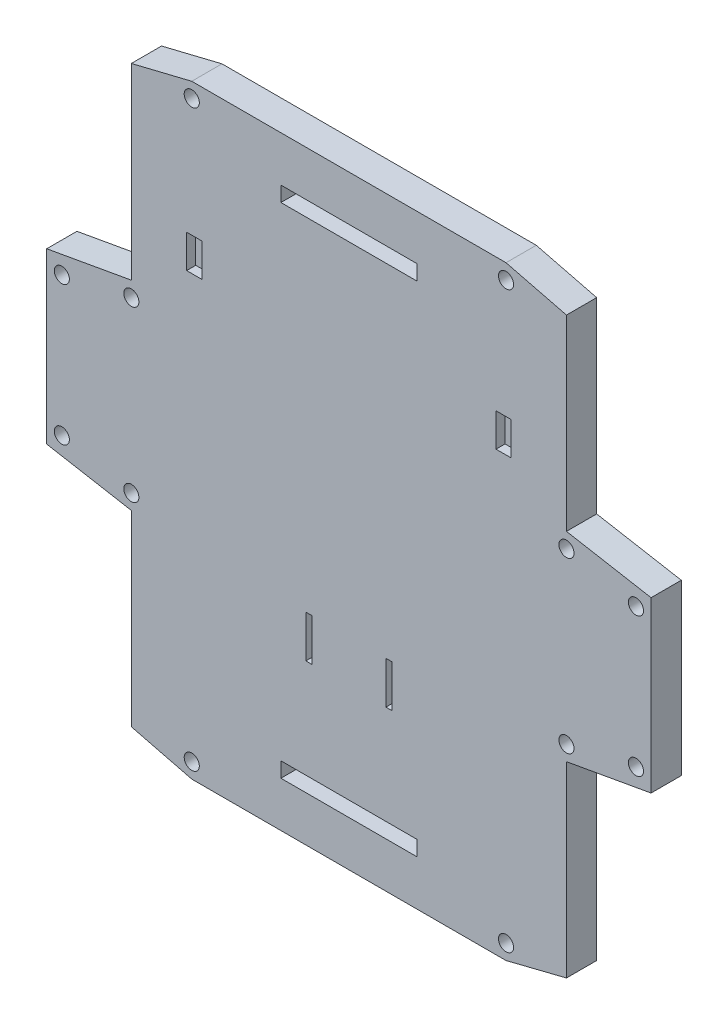
SolidWorks part; units mm, degrees
ref_plane "Front Plane" through (0, 0, 0) normal (0, 0, 1) x (1, 0, 0)
ref_plane "Top Plane" through (0, 0, 0) normal (0, 1, 0) x (1, 0, 0)
ref_plane "Right Plane" through (0, 0, 0) normal (1, 0, 0) x (0, 0, -1)
sketch "Sketch1" plane through (0, 0, 0) normal (0, 0, 1) x (1, 0, 0)
  line L1 (-52, 100) -> (52, 100)
  line L2 (-100, 28) -> (-100, -28)
  line L3 (-52, -100) -> (52, -100)
  line L4 (100, 28) -> (100, -28)
  line L5 (-72, 72) -> (72, -72) construction
  line L6 (-72, -72) -> (72, 72) construction
  line L7 (-72, -33) -> (-72, -95)
  line L9 (-72, 33) -> (-72, 95.1074)
  line L10 (-72, 33) -> (-100, 28)
  line L12 (72, 95) -> (72, 33)
  line L14 (72, -33) -> (72, -95)
  line L15 (72, 33) -> (100, 28)
  line L16 (-72, -33) -> (-100, -28)
  line L17 (72, -33) -> (100, -28)
  line L18 (-72, 95.1074) -> (-52, 100)
  line L19 (72, 95) -> (52, 100)
  line L20 (-72, -95) -> (-52, -100)
  line L21 (52, -100) -> (72, -95)
  line L22 (-52, 100) -> (-52, -100) construction
  line L23 (52, 100) -> (52, -100) construction
  point P0 (0, 0)
  dimension "D8" = 28
  dimension "D5" = 20
  dimension "D3" = 28
  dimension "D4" = 28
  dimension "D6" = 20
  dimension "D7" = 20
  dimension "D9" = 144
  dimension "D19" = 144
  dimension "D21" = 20
extrude "Boss-Extrude2" add sketch "Sketch1" along normal blind 15
sketch "Sketch2" plane through (0, 0, 15) normal (0, 0, 1) x (1, 0, 0)
  line L0 (-52, 100) -> (-52, -100) construction
  line L1 (52, 100) -> (52, -100) construction
  line L2 (-71, 95.352) -> (-68, 95.352) construction
  line L3 (-100, 28) -> (100, 28) construction
  line L4 (-100, -28) -> (100, -28) construction
  line L5 (71, 95.25) -> (71, -95.25) construction
  line L6 (72, 95) -> (52, 100) construction
  line L7 (52, -100) -> (72, -95) construction
  line L8 (72, 33) -> (72, 95) construction
  line L9 (-71, -95.25) -> (-68, -95.25) construction
  line L10 (-71, 95.352) -> (-71, -95.25) construction
  line L11 (-52, 100) -> (-72, 95.1074) construction
  line L12 (-72, -95) -> (-52, -100) construction
  line L13 (-72, 95.1074) -> (-72, 33) construction
  line L14 (-68, 96.0859) -> (-68, -96) construction
  line L15 (68, -96) -> (68, 96) construction
  line L16 (99, 28.1786) -> (99, -28.1786) construction
  line L17 (100, 28) -> (72, 33) construction
  line L18 (72, -33) -> (100, -28) construction
  line L19 (96, 28.7143) -> (96, -28.7143) construction
  line L20 (-99, -29.8888) -> (-99, 28.1786) construction
  line L21 (-72, 33) -> (-100, 28) construction
  line L22 (-71, 90.352) -> (-68, 90.352)
  line L23 (-96, 28.7143) -> (-96, -28.7143) construction
  line L24 (-100, -28) -> (-72, -33) construction
  line L25 (100, -28) -> (100, 28) construction
  line L26 (-100, 28) -> (-100, -28) construction
  line L27 (-68, 90.352) -> (-68, 70.352)
  line L28 (-52, -100) -> (52, -100) construction
  line L29 (-68, 70.352) -> (-71, 70.352)
  line L30 (-71, 70.352) -> (-71, 90.352)
  line L31 (-71, 33) -> (-68, 33)
  line L32 (-68, 33) -> (-68, 53)
  line L33 (-68, 53) -> (-71, 53)
  line L34 (-71, 53) -> (-71, 33)
  dimension "D1" = 1
  dimension "D2" = 1
  dimension "D3" = 3
  dimension "D4" = 3
  dimension "D5" = 1
  dimension "D6" = 3
  dimension "D7" = 1
  dimension "D8" = 3
  dimension "D9" = 190.602
  dimension "D10" = 200
  dimension "D11" = 192.0859
  dimension "D12" = 103.746
  dimension "D13" = 104.036
  dimension "D14" = 3
  dimension "D15" = 3
  dimension "D16" = 3
  dimension "D17" = 3.0923
  dimension "D18" = 3.0885
  dimension "D19" = 0.75
  dimension "D20" = 0.7339
  dimension "D21" = 56
  dimension "D22" = 67.352
  dimension "D23" = 67.25
  dimension "D24" = 5
  dimension "D25" = 20
  dimension "D26" = 5
  dimension "D27" = 20
extrude "Cut-Extrude2" cut sketch "Sketch2" against normal blind 10
sketch "Sketch4" plane through (0, 0, 15) normal (0, 0, 1) x (1, 0, 0)
  line L0 (-71, 90.352) -> (-68, 90.352)
  line L1 (-68, 90.352) -> (-68, 70.352)
  line L2 (-68, 70.352) -> (-69.5, 70.352)
  line L3 (-71, 70.352) -> (-68, 70.352) construction
  line L4 (-69.5, 70.352) -> (-71, 70.352)
  line L5 (-71, 70.352) -> (-71, 90.352)
  line L6 (-71, 53) -> (-68, 53)
  line L7 (-68, 53) -> (-68, 33)
  line L8 (-68, 33) -> (-71, 33)
  line L9 (-71, 33) -> (-71, 53)
extrude "Boss-Extrude5" add sketch "Sketch4" against normal blind 10
sketch "Sketch5" plane through (0, 0, 15) normal (0, 0, 1) x (1, 0, 0)
  line L0 (-72, 95.1074) -> (-72, 33)
  line L1 (-72, 33) -> (-100, 28)
  line L2 (-100, 28) -> (-100, -28)
  line L3 (-100, -28) -> (-72, -33)
  line L4 (-72, -33) -> (-72, -95)
  line L5 (-72, -95) -> (-52, -100)
  line L6 (-72, -95) -> (-52, -100) construction
  line L7 (-52, -100) -> (52, -100)
  line L8 (52, -100) -> (72, -95)
  line L9 (72, -95) -> (72, -33)
  line L10 (72, -33) -> (100, -28)
  line L11 (100, -28) -> (100, 28)
  line L12 (100, 28) -> (72, 33)
  line L13 (72, 33) -> (72, 95)
  line L14 (72, 95) -> (52, 100)
  line L15 (52, 100) -> (-52, 100)
  line L16 (-52, 100) -> (-72, 95.1074)
  line L17 (-52, -100) -> (52, -100) construction
  point P36 (0, -100)
extrude "Cut-Extrude3" cut sketch "Sketch5" against normal blind 5
sketch "Sketch6" plane through (0, 0, 10) normal (0, 0, 1) x (1, 0, 0)
  line L0 (-52, 100) -> (-52, -100) construction
  line L1 (52, 100) -> (52, -100) construction
  line L2 (-72, 95.1074) -> (72, 95) construction
  line L3 (-72, -95) -> (72, -95) construction
  line L4 (-72, -33) -> (-72, -95) construction
  line L5 (-100, 28) -> (100, 28) construction
  line L6 (-100, -28) -> (100, -28) construction
  line L7 (72, 33) -> (72, -33) construction
  line L8 (-72, 33) -> (-72, -33) construction
  line L9 (-100, 23) -> (100, 23) construction
  line L10 (-100, 28) -> (-100, -28) construction
  line L11 (100, -28) -> (100, 28) construction
  line L12 (-95, 28) -> (-95, -28) construction
  line L13 (95, 28) -> (95, -28) construction
  line L14 (67, 96.25) -> (67, -95) construction
  line L15 (72, 95) -> (52, 100) construction
  line L16 (-67, 96.3306) -> (-67, -96.25) construction
  line L17 (-52, 100) -> (-72, 95.1074) construction
  line L18 (-72, -95) -> (-52, -100) construction
  line L19 (72, 33) -> (72, 95) construction
  line L20 (-100, -23) -> (100, -23) construction
  circle A1 centre (-95, -23) radius 2.5
  circle A2 centre (-72, 28) radius 2.5
  circle A3 centre (-72, -28) radius 2.5
  circle A4 centre (-52, -95) radius 2.5
  circle A5 centre (52, -95) radius 2.5
  circle A6 centre (67, -28) radius 2.5
  circle A7 centre (72, 28) radius 2.5
  circle A8 centre (95, 23) radius 2.5
  circle A10 centre (-52, 95.0925) radius 2.5
  circle A11 centre (52, 95.0149) radius 2.5
  circle A12 centre (95, -23) radius 2.5
  circle A13 centre (-95, 23) radius 2.5
  dimension "D7" = 5
  dimension "D8" = 5
  dimension "D9" = 5
  dimension "D10" = 5
  dimension "D11" = 5
  dimension "D12" = 5
  dimension "D13" = 5
  dimension "D14" = 5
  dimension "D15" = 5
  dimension "D16" = 5
  dimension "D17" = 5
  dimension "D18" = 5
  dimension "D1" = 5
  dimension "D2" = 5
  dimension "D3" = 5
  dimension "D4" = 5
  dimension "D5" = 5
  dimension "D6" = 5
extrude "Cut-Extrude4" cut sketch "Sketch6" against normal blind 6
sketch "Sketch7" plane through (0, 0, 10) normal (0, 0, 1) x (1, 0, 0)
  line L0 (-72, -33) -> (72, -33) construction
  line L1 (-72, 33) -> (72, 33) construction
  line L2 (0, 100) -> (0, -100) construction
  line L3 (52, 100) -> (-52, 100) construction
  line L4 (-52, -100) -> (52, -100) construction
  circle M6 centre (67, -28) radius 2.5
extrude "Boss-Extrude6" add sketch "Sketch7" against normal blind 6 contours M6 region at (67, -28, 10)
sketch "Sketch8" plane through (0, 0, 10) normal (0, 0, 1) x (1, 0, 0)
  line L0 (0, 100) -> (0, -100) construction
  line L1 (52, 100) -> (-52, 100) construction
  line L2 (-52, -100) -> (52, -100) construction
  circle A2 centre (-72, -28) radius 2.5
  circle A3 centre (72, -28) radius 2.5
extrude "Cut-Extrude5" cut sketch "Sketch8" against normal blind 6
sketch "Sketch9" plane through (0, 0, 10) normal (0, 0, 1) x (1, 0, 0)
  line L0 (-72, -33) -> (72, -33) construction
  line L1 (72, -95) -> (72, -33) construction
  line L2 (0, 100) -> (0, -100) construction
  line L3 (52, 100) -> (-52, 100) construction
  line L4 (-52, -100) -> (52, -100) construction
  line L7 (-15, -24) -> (-15, -42)
  line L9 (15, -24) -> (15, -42)
  line L10 (-15, -24) -> (15, -42) construction
  line L11 (-15, -42) -> (15, -24) construction
  line L20 (-11.25, -27) -> (11.25, -39) construction
  line L21 (-11.25, -39) -> (11.25, -27) construction
  line L22 (-14.25, -26) -> (-12.25, -26)
  line L23 (-14.25, -26) -> (-14.25, -40)
  line L24 (-14.25, -40) -> (-12.25, -40)
  line L25 (-12.25, -26) -> (-12.25, -40)
  line L26 (-14.25, -26) -> (-12.25, -40) construction
  line L27 (-14.25, -40) -> (-12.25, -26) construction
  line L28 (12.25, -26) -> (14.25, -26)
  line L29 (12.25, -26) -> (12.25, -40)
  line L30 (12.25, -40) -> (14.25, -40)
  line L31 (14.25, -26) -> (14.25, -40)
  line L32 (12.25, -26) -> (14.25, -40) construction
  line L33 (12.25, -40) -> (14.25, -26) construction
  point P11 (0, -33)
  point P16 (0, -33)
  point P21 (-13.25, -33)
  point P26 (13.25, -33)
  dimension "D1" = 30
  dimension "D2" = 18
  dimension "D3" = 22.5
  dimension "D4" = 12
  dimension "D6" = 2
  dimension "D10" = 2
extrude "Cut-Extrude6" cut sketch "Sketch9" against normal blind 3 contours L31 L28 L29 L30 | L25 L22 L23 L24 region at (-13.25, -33, 10) region at (13.25, -33, 10)
sketch "Sketch10" plane through (0, 0, 10) normal (0, 0, 1) x (1, 0, 0)
  line L0 (0, 0) -> (0, 100) construction
  line L1 (52, 100) -> (-52, 100) construction
  line L2 (0, 100) -> (0, -100) construction
  line L3 (-52, -100) -> (52, -100) construction
  line L4 (-100, 0) -> (100, 0) construction
  line L5 (-72, 81.2) -> (72, 81.2) construction
  line L6 (-100, 28) -> (-100, -28) construction
  line L7 (100, -28) -> (100, 28) construction
  line L8 (-72, 95.1074) -> (72, 95) construction
  line L12 (-72, 95.1074) -> (-72, 33) construction
  line L13 (72, 33) -> (72, 95) construction
  line L21 (-53.69, 57.9) -> (-48.69, 57.9)
  line L22 (48.69, 57.9) -> (53.69, 57.9)
  line L23 (-53.69, 57.9) -> (-53.69, 46.9)
  line L24 (-53.69, 46.9) -> (-48.69, 46.9)
  line L25 (-48.69, 46.9) -> (-48.69, 57.9)
  line L26 (48.69, 57.9) -> (48.69, 46.9)
  line L27 (48.69, 46.9) -> (53.69, 46.9)
  line L29 (53.69, 57.9) -> (53.69, 46.9)
  dimension "D9" = 23.3
extrude "Cut-Extrude7" cut sketch "Sketch10" against normal blind 3
sketch "Sketch11" plane through (0, 0, 10) normal (0, 0, 1) x (1, 0, 0)
  line L0 (-53.69, 46.9) -> (-53.69, 44.9)
  line L1 (-53.69, 44.9) -> (-48.69, 44.9)
  line L2 (-48.69, 44.9) -> (-48.69, 46.9)
  line L3 (-48.69, 44.9) -> (-48.7646, 44.9)
  line L4 (-48.69, 57.9) -> (-53.69, 57.9) construction
  line L5 (-53.69, 55.9) -> (-48.69, 55.9)
  line L6 (-53.69, 57.9) -> (-53.69, 46.9) construction
  line L7 (-48.69, 46.9) -> (-48.69, 57.9) construction
  line L8 (-48.69, 55.9) -> (-48.69, 57.5499)
  line L9 (-48.69, 57.5499) -> (-48.69, 57.9)
  line L10 (-48.69, 57.9) -> (-53.69, 57.9)
  line L11 (-53.69, 57.9) -> (-53.69, 55.9)
  line L12 (-53.69, 46.9) -> (-48.69, 46.9) construction
  line L13 (48.69, 46.9) -> (48.69, 44.9)
  line L14 (48.69, 44.9) -> (53.69, 44.9)
  line L15 (53.69, 44.9) -> (53.69, 46.9)
  line L16 (53.69, 46.9) -> (53.69, 57.9) construction
  line L17 (53.69, 57.9) -> (48.69, 57.9)
  line L18 (48.69, 57.9) -> (48.69, 55.9)
  line L19 (48.69, 57.9) -> (48.69, 46.9) construction
  line L20 (48.69, 55.9) -> (53.69, 55.9)
  line L21 (53.69, 46.9) -> (53.69, 57.9) construction
  line L22 (53.69, 55.9) -> (53.69, 57.5499)
  line L23 (53.69, 57.5499) -> (53.69, 57.9)
  line L24 (48.69, 46.9) -> (53.69, 46.9) construction
  dimension "D1" = 2
  dimension "D2" = 2
  dimension "D3" = 2
  dimension "D4" = 2
extrude "Boss-Extrude8" add sketch "Sketch11" against normal blind 3 contours L10 L11 L5 L8 L9 | L20 L22 L23 L17 L18
sketch "Sketch12" plane through (0, 0, 10) normal (0, 0, 1) x (1, 0, 0)
  line L0 (-53.69, 46.9) -> (-48.69, 46.9)
  line L1 (-48.69, 46.9) -> (-48.69, 44.9)
  line L2 (-48.69, 44.9) -> (-53.69, 44.9)
  line L3 (-53.69, 44.9) -> (-53.69, 46.9)
  line L4 (53.69, 46.9) -> (48.69, 46.9)
  line L5 (48.69, 46.9) -> (48.69, 44.9)
  line L6 (48.69, 44.9) -> (53.69, 44.9)
  line L7 (53.69, 44.9) -> (53.69, 45.8783)
  line L8 (53.69, 45.8783) -> (53.69, 46.9)
  point P10 (51.19, 46.9)
  dimension "D1" = 2
  dimension "D2" = 2
extrude "Cut-Extrude8" cut sketch "Sketch12" against normal blind 3
ref_plane "Plane1" through (0, 0, 0) normal (1, 0, 0) x (0, 0, -1)
sketch "Sketch14" plane through (0, 0, 10) normal (0, 0, 1) x (1, 0, 0)
  line L0 (-48.69, 44.9) -> (-48.69, 55.9) construction
  line L1 (-53.69, 44.9) -> (-48.69, 44.9)
  line L2 (-53.69, 44.9) -> (-53.69, 52.15)
  line L3 (-53.69, 52.15) -> (-48.69, 52.15)
  line L4 (-48.69, 44.9) -> (-48.69, 52.15)
  dimension "D1" = 7.25
extrude "Boss-Extrude9" add sketch "Sketch14" against normal blind 3
sketch "Sketch15" plane through (0, 0, 10) normal (0, 0, 1) x (1, 0, 0)
  line L1 (-53.69, 55.9) -> (-48.69, 55.9)
  line L2 (-53.69, 55.9) -> (-53.69, 63.15)
  line L3 (-53.69, 63.15) -> (-48.69, 63.15)
  line L4 (-48.69, 55.9) -> (-48.69, 63.15)
  line L5 (-48.69, 52.15) -> (-48.69, 55.9) construction
  dimension "D1" = 7.25
extrude "Cut-Extrude9" cut sketch "Sketch15" against normal blind 3
sketch "Sketch16" plane through (0, 0, 10) normal (0, 0, 1) x (1, 0, 0)
  line L0 (53.69, 44.9) -> (53.69, 55.9) construction
  line L1 (48.69, 44.9) -> (53.69, 44.9)
  line L2 (48.69, 44.9) -> (48.69, 52.15)
  line L3 (48.69, 52.15) -> (53.69, 52.15)
  line L4 (53.69, 44.9) -> (53.69, 52.15)
  dimension "D1" = 7.25
extrude "Boss-Extrude10" add sketch "Sketch16" against normal blind 3
sketch "Sketch17" plane through (0, 0, 10) normal (0, 0, 1) x (1, 0, 0)
  line L0 (53.69, 55.9) -> (48.69, 55.9)
  line L1 (53.69, 55.9) -> (53.69, 63.15)
  line L2 (48.69, 55.9) -> (48.69, 63.15)
  line L3 (53.69, 63.15) -> (48.69, 63.15)
  dimension "D1" = 7.25
extrude "Cut-Extrude10" cut sketch "Sketch17" against normal blind 3
sketch "Sketch18" plane through (0, 0, 10) normal (0, 0, 1) x (1, 0, 0)
  line L0 (-53.69, 55.9) -> (-53.69, 63.15)
  line L1 (-53.69, 55.9) -> (-48.69, 55.9)
  line L2 (-53.69, 63.15) -> (-48.69, 63.15)
  line L3 (-48.69, 55.9) -> (-48.69, 63.15)
  line L4 (-53.69, 63.15) -> (-53.69, 52.15) construction
  line L5 (-53.69, 63.15) -> (-53.69, 52.15) construction
  line L7 (-48.69, 63.15) -> (-53.69, 63.15) construction
  line L8 (-48.69, 52.15) -> (-48.69, 63.15) construction
  point P6 (-51.19, 63.15)
  dimension "D1" = 7.25
  dimension "D2" = 0
  dimension "D3" = 0
extrude "Boss-Extrude11" add sketch "Sketch18" against normal blind 3
sketch "Sketch19" plane through (0, 0, 10) normal (0, 0, 1) x (1, 0, 0)
  line L0 (-53.69, 52.15) -> (-48.69, 52.15)
  line L1 (-53.69, 52.15) -> (-53.69, 44.9)
  line L2 (-48.69, 52.15) -> (-48.69, 44.9)
  line L3 (-53.69, 44.9) -> (-48.69, 44.9)
  dimension "D1" = 7.25
extrude "Cut-Extrude11" cut sketch "Sketch19" against normal blind 3
sketch "Sketch20" plane through (0, 0, 10) normal (0, 0, 1) x (1, 0, 0)
  line L0 (48.69, 52.15) -> (53.69, 52.15)
  line L1 (48.69, 52.15) -> (48.69, 44.9)
  line L3 (48.69, 44.9) -> (53.69, 44.9)
  line L4 (48.69, 63.15) -> (48.69, 52.15) construction
  line L5 (48.69, 63.15) -> (53.69, 63.15)
  line L6 (48.69, 63.15) -> (48.69, 55.9)
  line L7 (53.69, 63.15) -> (53.69, 55.9)
  line L8 (48.69, 55.9) -> (53.69, 55.9)
  line M7 (48.69, 63.15) -> (53.69, 63.15)
  line M8 (53.69, 63.15) -> (53.69, 52.15)
  line M10 (48.69, 52.15) -> (48.69, 63.15)
  dimension "D1" = 7.25
  dimension "D2" = 7.25
extrude "Boss-Extrude12" add sketch "Sketch20" against normal blind 3 contours L8 M10 M8 M7 region at (51.19, 59.525, 10)
sketch "Sketch21" plane through (0, 0, 10) normal (0, 0, 1) x (1, 0, 0)
  line L0 (48.69, 52.15) -> (53.69, 52.15)
  line L5 (48.69, 52.15) -> (48.69, 44.9)
  line L6 (53.69, 52.15) -> (53.69, 44.9)
  line L7 (48.69, 44.9) -> (53.69, 44.9)
  dimension "D1" = 7.25
extrude "Cut-Extrude12" cut sketch "Sketch21" against normal blind 3
sketch "Sketch22" plane through (0, 0, 10) normal (0, 0, 1) x (1, 0, 0)
  line L0 (-14.25, -40) -> (-12.25, -40)
  line L1 (-14.25, -40) -> (-14.25, -47.25)
  line L2 (-12.25, -40) -> (-12.25, -47.25)
  line L3 (-14.25, -47.25) -> (-12.25, -47.25)
  line L4 (12.25, -40) -> (14.25, -40)
  line L5 (12.25, -40) -> (12.25, -47.25)
  line L6 (14.25, -40) -> (14.25, -47.25)
  line L7 (12.25, -47.25) -> (14.25, -47.25)
  dimension "D1" = 7.25
  dimension "D2" = 7.25
extrude "Cut-Extrude13" cut sketch "Sketch22" against normal blind 3
sketch "Sketch23" plane through (0, 0, 10) normal (0, 0, 1) x (1, 0, 0)
  line L0 (-14.25, -26) -> (-12.25, -26)
  line L1 (-14.25, -26) -> (-14.25, -33.25)
  line L2 (-12.25, -26) -> (-12.25, -33.25)
  line L3 (-14.25, -33.25) -> (-12.25, -33.25)
  line L4 (12.25, -26) -> (14.25, -26)
  line L5 (12.25, -26) -> (12.25, -33.25)
  line L6 (14.25, -26) -> (14.25, -33.25)
  line L7 (12.25, -33.25) -> (14.25, -33.25)
  dimension "D1" = 7.25
  dimension "D2" = 7.25
extrude "Boss-Extrude13" add sketch "Sketch23" against normal blind 3
sketch "Sketch24" plane through (0, 0, 10) normal (0, 0, 1) x (1, 0, 0)
  line L0 (-52, 100) -> (-52, -100) construction
  line L1 (52, 100) -> (52, -100) construction
  line L2 (-72, 95.1074) -> (72, 95) construction
  line L4 (-72, -95) -> (72, -95) construction
  line L5 (0, 100) -> (0, -100) construction
  line L6 (52, 100) -> (-52, 100) construction
  line L7 (-52, -100) -> (52, -100) construction
  line L9 (-22.5, 97.5537) -> (22.5, 97.5537)
  line L10 (-22.5, 97.5537) -> (-22.5, 92.5537)
  line L11 (-22.5, 92.5537) -> (22.5, 92.5537)
  line L12 (22.5, 97.5537) -> (22.5, 92.5537)
  line L13 (-22.5, 97.5537) -> (22.5, 92.5537) construction
  line L14 (-22.5, 92.5537) -> (22.5, 97.5537) construction
  line L15 (-22.5, -92.5) -> (22.5, -92.5)
  line L16 (-22.5, -92.5) -> (-22.5, -97.5)
  line L17 (-22.5, -97.5) -> (22.5, -97.5)
  line L18 (22.5, -92.5) -> (22.5, -97.5)
  line L19 (-22.5, -92.5) -> (22.5, -97.5) construction
  line L20 (-22.5, -97.5) -> (22.5, -92.5) construction
  point P26 (0, 95.0537)
  point P31 (0, -95)
  dimension "D1" = 45
  dimension "D2" = 5
  dimension "D3" = 45
  dimension "D4" = 5
extrude "Cut-Extrude14" cut sketch "Sketch24" against normal blind 5
sketch "Sketch25" plane through (0, 0, 5) normal (0, 0, 1) x (1, 0, 0)
  line L1 (-22.5, 92.5537) -> (22.5, 92.5537)
  line L2 (-22.5, 92.5537) -> (-22.5, 97.5537)
  line L3 (-22.5, 97.5537) -> (22.5, 97.5537)
  line L4 (22.5, 92.5537) -> (22.5, 97.5537)
  line L9 (-22.5, -97.5) -> (22.5, -97.5)
  line L10 (-22.5, -97.5) -> (-22.5, -92.5)
  line L11 (-22.5, -92.5) -> (22.5, -92.5)
  line L12 (22.5, -97.5) -> (22.5, -92.5)
extrude "Boss-Extrude17" add sketch "Sketch25" along normal blind 5
sketch "Sketch26" plane through (0, 0, 10) normal (0, 0, 1) x (1, 0, 0)
  line L0 (0, 100) -> (0, -100) construction
  line L1 (52, 100) -> (-52, 100) construction
  line L2 (-52, -100) -> (52, -100) construction
  line L3 (-100, 0) -> (100, 0) construction
  line L4 (72, -95) -> (-72, -95) construction
  line L7 (72, 95) -> (-72, 95.1074) construction
  line L16 (-22.5, -80) -> (22.5, -80)
  line L17 (-22.5, -80) -> (-22.5, -85)
  line L18 (-22.5, -85) -> (22.5, -85)
  line L19 (22.5, -80) -> (22.5, -85)
  line L20 (-22.5, -80) -> (22.5, -85) construction
  line L21 (-22.5, -85) -> (22.5, -80) construction
  line L22 (-100, 28) -> (-100, -28) construction
  line L23 (100, -28) -> (100, 28) construction
  line L24 (-22.5, 80) -> (-22.5, 85)
  line L25 (-22.5, 80) -> (22.5, 80)
  line L26 (-22.5, 85) -> (22.5, 85)
  line L27 (22.5, 80) -> (22.5, 85)
  point P7 (0, 83.2013)
  point P19 (0, -82.5)
  dimension "D1" = 10
  dimension "D3" = 45
  dimension "D5" = 5
extrude "Cut-Extrude16" cut sketch "Sketch26" against normal blind 5
